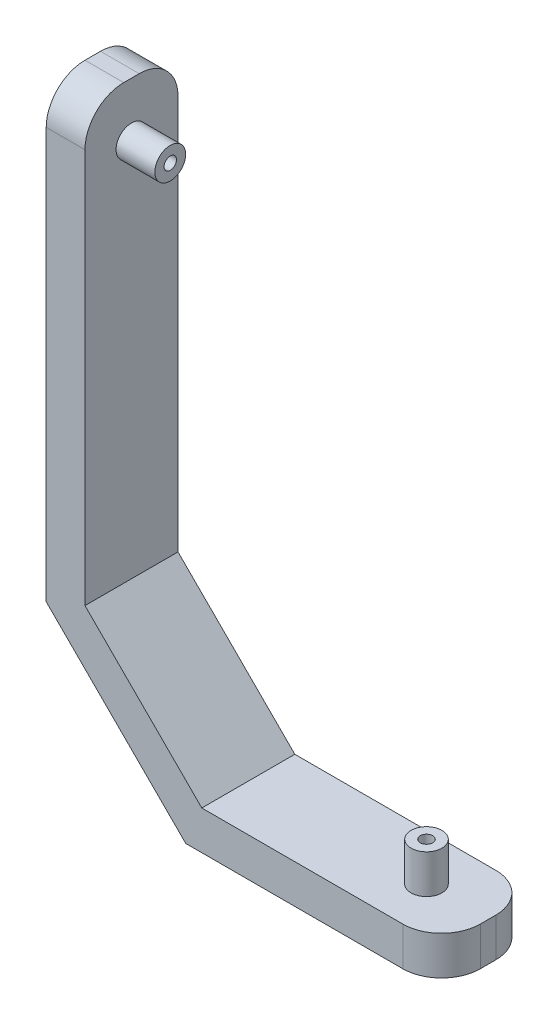
SolidWorks part; units mm, degrees
ref_plane "Front Plane" through (0, 0, 0) normal (0, 0, 1) x (1, 0, 0)
ref_plane "Top Plane" through (0, 0, 0) normal (0, 1, 0) x (1, 0, 0)
ref_plane "Right Plane" through (0, 0, 0) normal (1, 0, 0) x (0, 0, -1)
sketch "Sketch11" plane through (0, 0, 0) normal (0, 0, 1) x (1, 0, 0)
  line L0 (-76.2, 30.1421) -> (-46.0579, 0)
  line L1 (-76.2, 142) -> (-86.2, 142)
  line L2 (-76.2, 142) -> (-76.2, 26)
  line L3 (-76.2, 26) -> (-86.2, 26)
  line L4 (-86.2, 142) -> (-86.2, 26)
  line L5 (15.8, 0) -> (-50.2, 0)
  line L6 (15.8, 0) -> (15.8, -10)
  line L7 (15.8, -10) -> (-50.2, -10)
  line L8 (-50.2, 0) -> (-50.2, -10)
  line L9 (-50.2, -10) -> (-86.2, 26)
  point P4 (0, 0)
  point P5 (13.4189, -3.3751)
  point P10 (3.6481, 7.1528)
  point P11 (0, 0)
  point P14 (7.0627, -8.3493)
  dimension "D1" = 10
  dimension "D2" = 102
  dimension "D3" = 152
  dimension "D4" = 45
  dimension "D5" = 10
  dimension "D6" = 10
  dimension "D7" = 66
  dimension "D8" = 15.8
extrude "Boss-Extrude7" add sketch "Sketch11" against normal blind 12 and the other way blind 12 contours L9 L8 L5 L0 L2 L3 | L1 L4 L2 | L7 L6 L5 L8 region at (-81.2, 84, 0) region at (-64.8264, 11.3736, 0)
fillet "Fillet1" radius 10 4 edges at (-81.2, 142, -12) (15.8, -5, -12) (15.8, -5, 12) (-81.2, 142, 12)
sketch "Sketch1" plane through (-76.2, 0, 0) normal (1, 0, 0) x (0, 0, -1)
  line L0 (2, 142) -> (-2, 142) construction
  circle A1 centre (0, 128) radius 3.98
  point P6 (0, 142)
  dimension "D1" = 14
  dimension "D2" = 7.96
extrude "Boss-Extrude3" add sketch "Sketch1" along normal blind 10
sketch "Sketch5" plane through (-66.2, 0, 0) normal (1, 0, 0) x (0, 0, -1)
  circle A0 centre (0, 128) radius 1.6
  circle A1 centre (0, 128) radius 3.98 construction
  dimension "D1" = 3.2
extrude "Cut-Extrude1" cut sketch "Sketch5" against normal through all
sketch "Sketch6" plane through (-86.2, 0, 0) normal (-1, 0, 0) x (0, 0, 1)
  circle A0 centre (0, 128) radius 2
  circle A1 centre (0, 128) radius 1.6 construction
extrude "Cut-Extrude2" cut sketch "Sketch6" against normal blind 3
sketch "Sketch7" plane through (0, 0, 0) normal (0, 1, 0) x (1, 0, 0)
  line L0 (15.8, 2) -> (15.8, -2) construction
  circle A1 centre (-0.0882, 0) radius 3.98
  point P5 (15.8, 0)
  dimension "D1" = 7.96
  dimension "D2" = 15.8882
extrude "Boss-Extrude5" add sketch "Sketch7" along normal blind 10
sketch "Sketch9" plane through (0, 10, 0) normal (0, 1, 0) x (1, 0, 0)
  circle A0 centre (-0.0882, 0) radius 1.6
  dimension "D1" = 3.2
extrude "Cut-Extrude3" cut sketch "Sketch9" against normal blind 17
sketch "Sketch10" plane through (0, -10, 0) normal (0, -1, 0) x (1, 0, 0)
  circle A0 centre (-0.0882, 0) radius 4
  dimension "D1" = 8
extrude "Cut-Extrude4" cut sketch "Sketch10" against normal blind 3
sketch "Sketch12" plane through (0, 0, 0) normal (0, 0, 1) x (1, 0, 0)
  line L0 (0, 0) -> (-76.2, 0)
  line L1 (-76.2, 0) -> (-76.2, 128)
  line L2 (-76.2, 124.02) -> (-76.2, 131.98) construction
